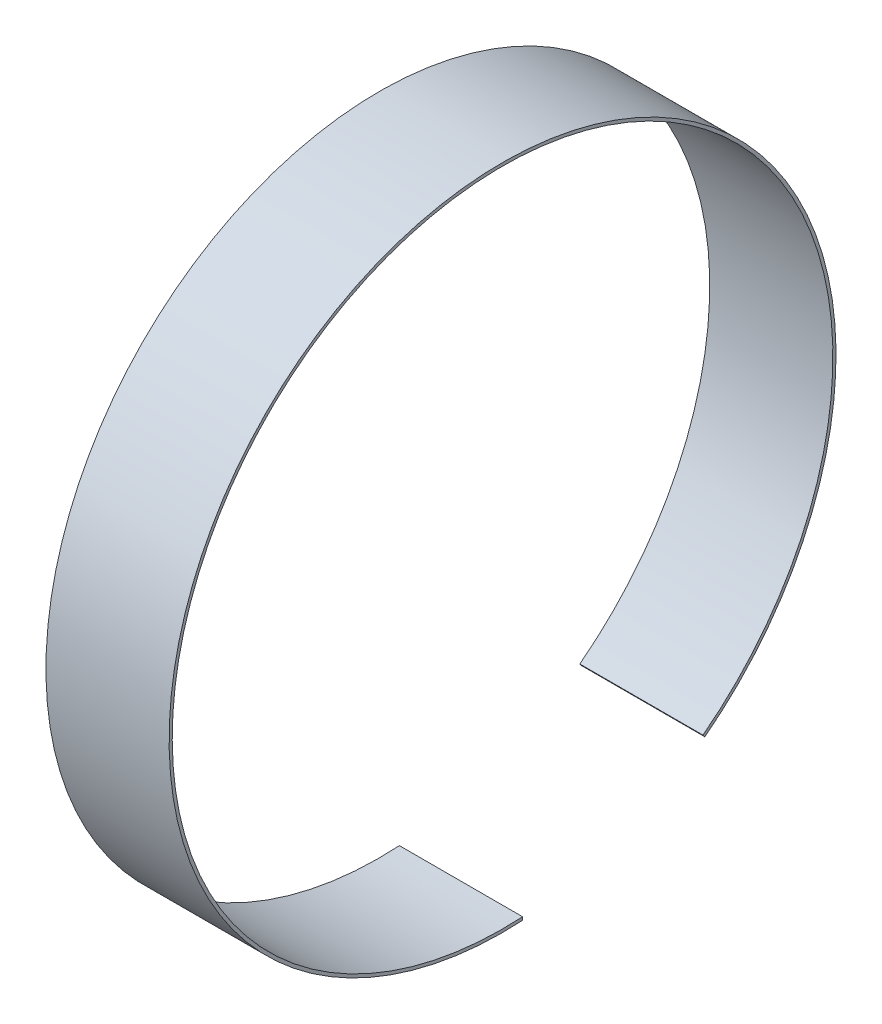
SolidWorks part; units mm, degrees
ref_plane "Front Plane" through (0, 0, 0) normal (0, 0, 1) x (1, 0, 0)
ref_plane "Top Plane" through (0, 0, 0) normal (0, 1, 0) x (1, 0, 0)
ref_plane "Right Plane" through (0, 0, 0) normal (1, 0, 0) x (0, 0, -1)
sketch "Sketch1" plane through (0, 0, 0) normal (1, 0, 0) x (0, 0, -1)
  line L0 (4.5, -55.7107) -> (4.5, -85.7107)
  line L1 (4.5, -55.7107) -> (45.5, -55.7107)
  line L2 (4.5, -85.7107) -> (45.5, -85.7107)
  line L3 (45.5, -55.7107) -> (45.5, -85.7107)
  line L4 (4.5, -55.7107) -> (45.5, -85.7107) construction
  line L5 (4.5, -85.7107) -> (45.5, -55.7107) construction
  line L6 (4.5, -74.8649) -> (4.458, -74.1661)
  line L7 (45.5, -59.6217) -> (45.0753, -59.0653)
  circle A0 centre (0, 0) radius 75
  circle A1 centre (0, 0) radius 74.3
  point P5 (25, -70.7107)
  point P13 (0, 0)
  point P14 (22.4222, -71.5698)
  dimension "D1" = 150
  dimension "D2" = 0.7
  dimension "D3" = 41
  dimension "D4" = 30
  dimension "D5" = 25
extrude "Boss-Extrude1" add sketch "Sketch1" along normal mid plane 27.7 contours A1 L3 A0 L6 | A1 L6 L0 | A1 L7 L3 region at (0, -74.3982, -4.486) region at (0, 51.272, 54.4464) region at (0, -59.1421, -45.3585)
